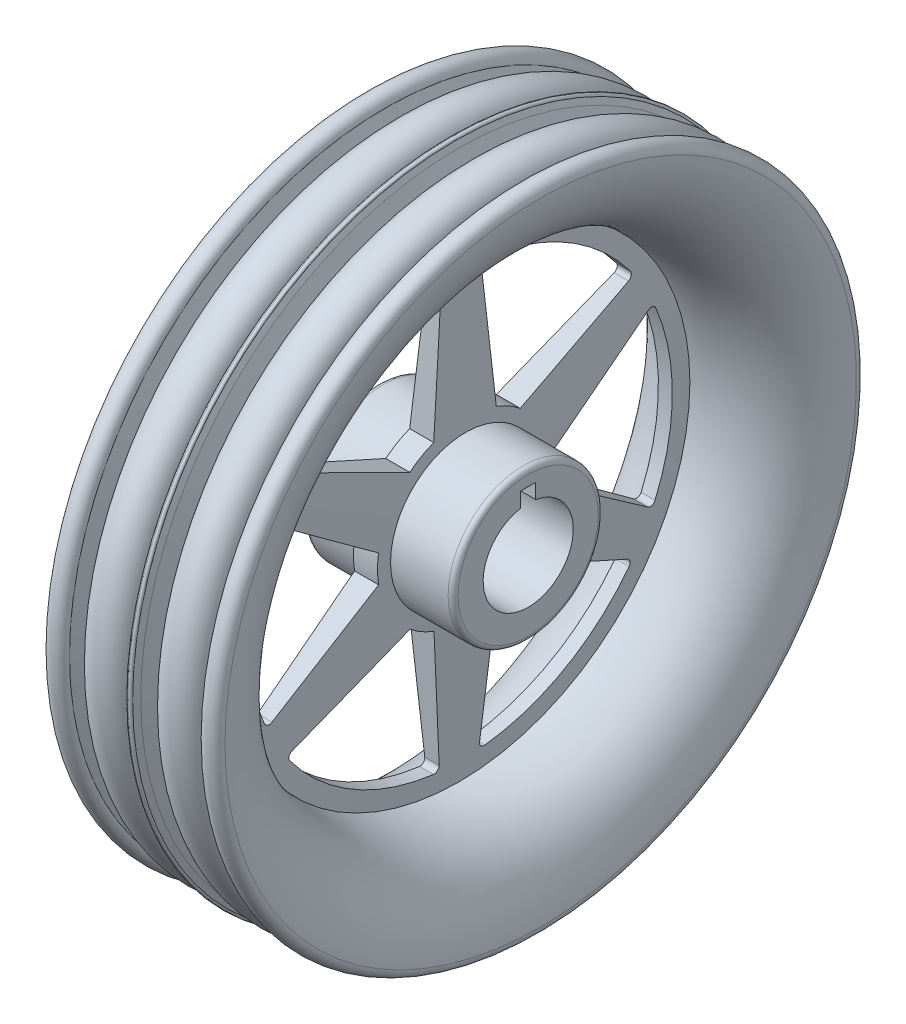
SolidWorks part; units mm, degrees
ref_plane "Front Plane" through (0, 0, 0) normal (0, 0, 1) x (1, 0, 0)
ref_plane "Top Plane" through (0, 0, 0) normal (0, 1, 0) x (1, 0, 0)
ref_plane "Right Plane" through (0, 0, 0) normal (1, 0, 0) x (0, 0, -1)
sketch "Sketch1" plane through (0, 0, 0) normal (0, 1, 0) x (1, 0, 0)
  line L0 (-45.0773, 0) -> (44.6134, 0) construction
  line L1 (-30, 18) -> (30, 18)
  line L2 (0, 72.6785) -> (0, -27.9897) construction
  line L3 (-30, 18) -> (-30, 28)
  line L4 (-28, 30) -> (-5, 30)
  line L5 (30, 28) -> (30, 18)
  line L6 (-2.006, 126.7929) -> (-1.0848, 129.0169)
  line L7 (5, 30) -> (28, 30)
  line L8 (-30, 18) -> (-31, 18)
  line L10 (-31, 18) -> (-31, 15)
  line L11 (-31, 15) -> (31, 15)
  line L13 (31, 15) -> (31, 18)
  line L14 (31, 18) -> (30, 18)
  line L15 (-45.2089, 119.9543) -> (50.3476, 119.9543) construction
  line L17 (2.006, 126.7929) -> (11.1017, 104.834)
  line L19 (0, 72.6785) -> (0, 149.8944) construction
  line L20 (0.9857, 129.0169) -> (2.006, 126.7929)
  line L25 (14.6099, 142.6474) -> (14.6099, 78.1249) construction
  line L26 (-45.2089, 129.9543) -> (47.2447, 129.9543) construction
  line L27 (27.0007, 126.2782) -> (18.8095, 106.503)
  line L28 (-2.006, 126.7929) -> (-11.1017, 104.834)
  line L29 (-27.0007, 126.2782) -> (-18.8194, 106.5268)
  line L32 (2.4694, 92.1174) -> (5, 30)
  line L33 (-5, 30) -> (-2.4978, 92.1194)
  arc A0 (5, 30) -> (-5, 30) centre (0, 30) ccw
  arc A1 (28, 30) -> (30, 28) centre (28, 28) cw
  arc A2 (-30, 28) -> (-28, 30) centre (-28, 28) cw
  arc A4 (-27.0007, 126.2782) -> (-34.9886, 126.1386) centre (-30.991, 126.0006) ccw
  arc A6 (34.9886, 126.1386) -> (2.4694, 92.1174) centre (0, 127.0302) cw
  arc A10 (-2.4978, 92.1194) -> (-34.9886, 126.1386) centre (0, 127.0302) cw
  arc A11 (11.1017, 104.834) -> (18.8095, 106.503) centre (14.8042, 106.3676) ccw
  arc A12 (-18.8194, 106.5268) -> (-11.1017, 104.834) centre (-14.3707, 108.3696) ccw
  arc A13 (0.9857, 129.0169) -> (0, 129.9543) centre (0.0471, 129.0169) ccw
  arc A14 (2.4694, 92.1174) -> (-2.4694, 92.1174) centre (0, 90.6374) ccw
  arc A15 (0, 129.9543) -> (-1.0848, 129.0169) centre (0.0585, 128.7903) ccw
  arc A16 (27.0007, 126.2782) -> (34.9886, 126.1386) centre (30.991, 126.0006) cw
  circle A17 centre (14.6099, 119.9543) radius 9.0275
  circle A18 centre (-14.6099, 119.9543) radius 9.0275
  point P19 (31.0609, 130)
  dimension "D4" = 2
  dimension "D6" = 4.0076
  dimension "D11" = 4.8153
  dimension "D14" = 2.4694
  dimension "D15" = 11.1017
  dimension "D5" = 4
  dimension "D18" = 45
  dimension "D19" = 35
  dimension "D20" = 2.879
  dimension "D2" = 5
  dimension "D21" = 1.1655
  dimension "D22" = 0.0471
  dimension "D23" = 30
  dimension "D13" = 0.9386
  dimension "D1" = 15
  dimension "D3" = 30
  dimension "D7" = 2.006
  dimension "D8" = 62
  dimension "D9" = 45
  dimension "D10" = 130
  dimension "D12" = 25
  dimension "D16" = 14.6099
  dimension "D17" = 3
  dimension "D24" = 30.991
  dimension "D25" = 31.0609
  dimension "D26" = 10
  dimension "D32" = 2.4978
revolve "Revolve3" add sketch "Sketch1" angle 360 about L0 region at (0, 0, -24.4084) region at (-0.0781, 0, -96.6668)
sketch "Sketch2" plane through (-30, 0, 0) normal (-1, 0, 0) x (0, 0, 1)
  line L0 (0, 136.2539) -> (0, -148.2061) construction
  line L1 (-153.0916, 0) -> (147.1194, 0) construction
  line L2 (74.9084, 34.3681) -> (34.5712, 5.4618)
  line L3 (22.108, 27.1337) -> (66.7895, 48.3136)
  line L4 (67.2178, -47.6886) -> (22.0156, -27.2087)
  line L5 (34.5524, -5.5793) -> (75.2355, -33.6846)
  line L6 (-7.6906, -82.0566) -> (-12.5556, -32.6704)
  line L7 (12.4444, -32.7129) -> (8.4461, -81.9982)
  line L8 (-12.4444, 32.7129) -> (-8.4461, 81.9982)
  line L9 (7.6906, 82.0566) -> (12.5556, 32.6704)
  line L10 (-74.9084, -34.3681) -> (-34.5712, -5.4618)
  line L11 (-22.108, -27.1337) -> (-66.7895, -48.3136)
  line L12 (-67.2178, 47.6886) -> (-22.0156, 27.2087)
  line L13 (-34.5524, 5.5793) -> (-75.2355, 33.6846)
  arc A0 (66.7895, 48.3136) -> (67.525, 51.3312) centre (65.9328, 50.1208) ccw
  arc A1 (-10.6916, 84.1439) -> (-67.9957, 50.7059) centre (0, 0) ccw
  arc A2 (-12.4444, 32.7129) -> (-22.0156, 27.2087) centre (0, 0) ccw
  arc A3 (7.6906, 82.0566) -> (9.9147, 84.239) centre (9.681, 82.2527) cw
  arc A4 (-8.4461, 81.9982) -> (-10.6916, 84.1439) centre (-10.4395, 82.1599) ccw
  arc A5 (74.9084, 34.3681) -> (77.9105, 33.5331) centre (76.0734, 32.7424) cw
  arc A6 (75.2355, -33.6846) -> (78.2166, -32.8128) centre (76.3723, -32.0391) ccw
  arc A7 (67.2178, -47.6886) -> (67.9957, -50.7059) centre (66.3925, -49.5103) cw
  arc A8 (8.4461, -81.9982) -> (10.6916, -84.1439) centre (10.4395, -82.1599) ccw
  arc A9 (-7.6906, -82.0566) -> (-9.9147, -84.239) centre (-9.681, -82.2527) cw
  arc A10 (-66.7895, -48.3136) -> (-67.525, -51.3312) centre (-65.9328, -50.1208) ccw
  arc A11 (-74.9084, -34.3681) -> (-77.9105, -33.5331) centre (-76.0734, -32.7424) cw
  arc A12 (-75.2355, 33.6846) -> (-78.2166, 32.8128) centre (-76.3723, 32.0391) ccw
  arc A13 (-67.2178, 47.6886) -> (-67.9957, 50.7059) centre (-66.3925, 49.5103) cw
  arc A14 (-34.5524, 5.5793) -> (-34.5712, -5.4618) centre (0, 0) ccw
  arc A15 (-78.2166, 32.8128) -> (-77.9105, -33.5331) centre (0, 0) ccw
  arc A16 (-22.108, -27.1337) -> (-12.5556, -32.6704) centre (0, 0) ccw
  arc A17 (-67.525, -51.3312) -> (-9.9147, -84.239) centre (0, 0) ccw
  arc A18 (12.4444, -32.7129) -> (22.0156, -27.2087) centre (0, 0) ccw
  arc A19 (10.6916, -84.1439) -> (67.9957, -50.7059) centre (0, 0) ccw
  arc A20 (78.2166, -32.8128) -> (77.9105, 33.5331) centre (0, 0) ccw
  arc A21 (34.5524, -5.5793) -> (34.5712, 5.4618) centre (0, 0) ccw
  arc A22 (22.108, 27.1337) -> (12.5556, 32.6704) centre (0, 0) ccw
  arc A23 (67.525, 51.3312) -> (9.9147, 84.239) centre (0, 0) ccw
  point P58 (0, 0)
  dimension "D1" = 2
  dimension "D2" = 6
extrude "Cut-Extrude1" cut sketch "Sketch2" against normal through all both and the other way through all contours A1 A13 L12 A2 L8 A4 | A3 A23 A0 L3 A22 L9 | A6 A20 A5 L2 A21 L5 | L7 A8 A19 A7 L4 A18 | A10 A17 A9 L6 A16 L11 | A12 A15 A11 L10 A14 L13
sketch "Sketch3" plane through (30, 0, 0) normal (1, 0, 0) x (0, 0, -1)
  line L0 (0, 48.8172) -> (0, 0) construction
  line L1 (3, 17.7482) -> (3, 23.7482)
  line L2 (3, 23.7482) -> (-3, 23.7482)
  line L3 (-3, 23.7482) -> (-3, 17.7482)
  circle A0 centre (0, 0) radius 18 construction
  arc A1 (-3, 17.7482) -> (3, 17.7482) centre (0, 0) ccw
  dimension "D1" = 6
  dimension "D2" = 6
extrude "Cut-Extrude2" cut sketch "Sketch3" against normal through all both
revolve "Revolve4" add sketch "Sketch1<3>" angle 360 about L0 region at (-14.6099, 0, -119.9543) region at (14.6099, 0, -119.9543)
sketch "Sketch1<3>" plane through (0, 0, 0) normal (0, 1, 0) x (1, 0, 0) same geometry as "Sketch1"
